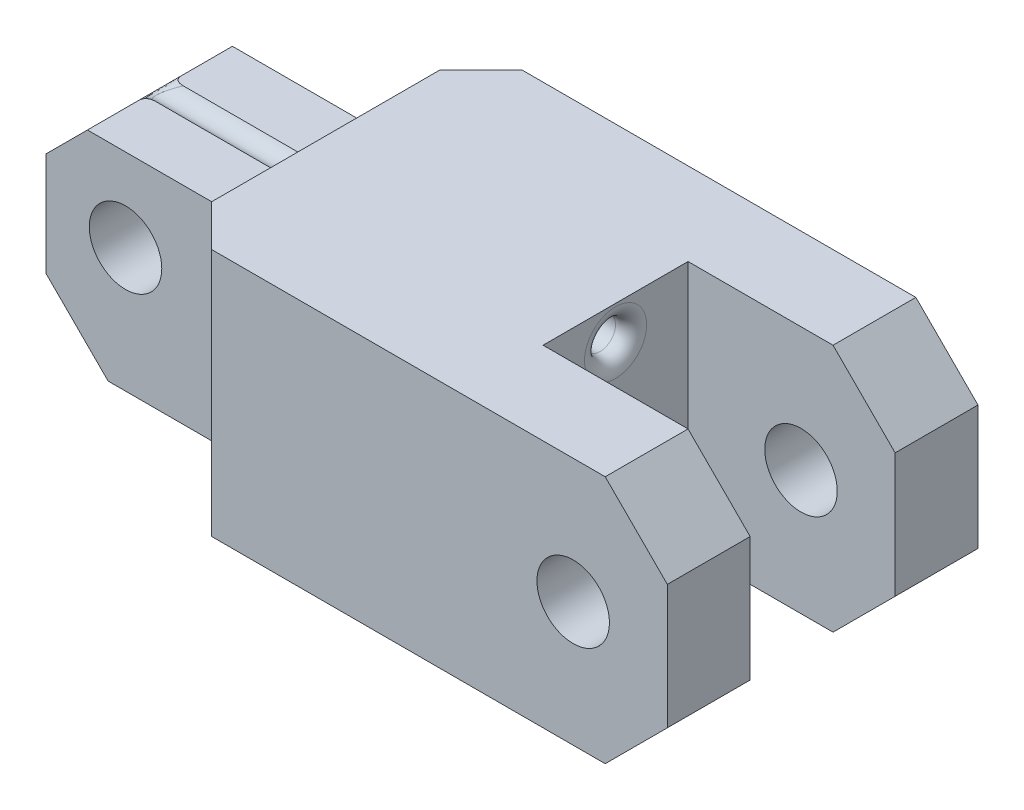
SolidWorks part; units mm, degrees
ref_plane "Спереди" through (0, 0, 0) normal (0, 0, 1) x (1, 0, 0)
ref_plane "Сверху" through (0, 0, 0) normal (0, 1, 0) x (1, 0, 0)
ref_plane "Справа" through (0, 0, 0) normal (1, 0, 0) x (0, 0, -1)
sketch "Эскиз2" plane through (0, 0, 0) normal (1, 0, 0) x (0, 0, -1)
  line L1 (-7.5, 6) -> (7.5, 6)
  line L2 (-7.5, 6) -> (-7.5, -6)
  line L3 (-7.5, -6) -> (7.5, -6)
  line L4 (7.5, 6) -> (7.5, -6)
  line L5 (-7.5, 6) -> (7.5, -6) construction
  line L6 (-7.5, -6) -> (7.5, 6) construction
  point P0 (0, 0)
extrude "Вытянуть1" add sketch "Эскиз2" along normal blind 34
sketch "Эскиз3" plane through (0, 6, 0) normal (0, 1, 0) x (1, 0, 0)
  line L0 (0, 0) -> (-9.2006, 0) construction
  line L1 (10, -9.9613) -> (10, -3.5)
  line L2 (-3.345, 9.9613) -> (10, 9.9613)
  line L3 (-3.345, 9.9613) -> (-3.345, 3.5)
  line L4 (-3.345, 3.5) -> (10, 3.5)
  line L5 (10, 9.9613) -> (10, 3.5)
  line L6 (-3.345, -9.9613) -> (10, -9.9613)
  line L7 (-3.345, -3.5) -> (10, -3.5)
  line L8 (-3.345, -9.9613) -> (-3.345, -3.5)
  line L9 (0, 7.5) -> (0, -7.5) construction
  dimension "D1" = 3.5
  dimension "D2" = 10
extrude "Вырез-Вытянуть1" cut sketch "Эскиз3" against normal through all
sketch "Эскиз4" plane through (0, 0, 3.5) normal (0, 0, 1) x (1, 0, 0)
  circle A0 centre (3.8399, 0) radius 1.75
extrude "Вытянуть2" cut sketch "Эскиз4" against normal through all
sketch "Эскиз5" plane through (0, 6, 0) normal (0, 1, 0) x (1, 0, 0)
  line L0 (40, 0) -> (51.6105, 0) construction
  line L2 (34, 7.5) -> (34, -7.5) construction
  line L3 (24, 3.5) -> (45.3677, 3.5)
  line L4 (24, 3.5) -> (24, -3.5)
  line L5 (24, -3.5) -> (45.3677, -3.5)
  line L6 (45.3677, 3.5) -> (45.3677, -3.5)
  line L7 (24, 3.5) -> (45.3677, -3.5) construction
  line L8 (24, -3.5) -> (45.3677, 3.5) construction
  point P1 (34.6838, 0)
  dimension "D1" = 10
extrude "Вырез-Вытянуть2" cut sketch "Эскиз5" against normal through all
chamfer "Фаска4" distance 3 angle 45 4 edges at (34, -6, -5.5) (34, -6, 5.5) (34, 6, -5.5) (34, 6, 5.5)
sketch "Эскиз7" plane through (24, 0, 0) normal (1, 0, 0) x (0, 0, -1)
  line L0 (0, 6) -> (0, 3.9395) construction
  circle A0 centre (0, 4.3577) radius 0.75
extrude "Вытянуть3" cut sketch "Эскиз7" against normal through all
chamfer "Фаска5" distance 3 angle 45 1 edges at (0, -6, 0)
sketch "Эскиз8" plane through (0, 0, 0) normal (-1, 0, 0) x (0, 0, 1)
  line L0 (0, 6) -> (0, 2.0994) construction
  line L2 (-3.5, 6) -> (-7.5, 6) construction
  line L3 (-3.9395, 7.8642) -> (3.9729, 7.8642)
  line L4 (-3.9395, 7.8642) -> (-3.9395, 4)
  line L5 (-3.9395, 4) -> (3.9729, 4)
  line L6 (3.9729, 7.8642) -> (3.9729, 4)
  dimension "D1" = 2
extrude "Вытянуть4" cut sketch "Эскиз8" against normal blind 10
chamfer "Фаска6" distance 2 angle 45 2 edges at (0, 4, 2.0796) (0, 4, -2.0796)
fillet "Скругление1" radius 0.75 2 edges at (10, 5.1077, 0) (24, 4.3577, -0.75)
sketch "Эскиз9" plane through (0, 0, 7.5) normal (0, 0, 1) x (1, 0, 0)
  line L0 (30.3754, 0) -> (53.7127, 0) construction
  circle A0 centre (29.4543, 0) radius 1.75
extrude "Вырез-Вытянуть3" cut sketch "Эскиз9" against normal through all
fillet "Скругление2" radius 0.5 1 edges at (1.6077, 3.6077, 0)
chamfer "Фаска8" distance 2 angle 45 2 edges at (10, 0, -7.5) (10, 0, 7.5)
